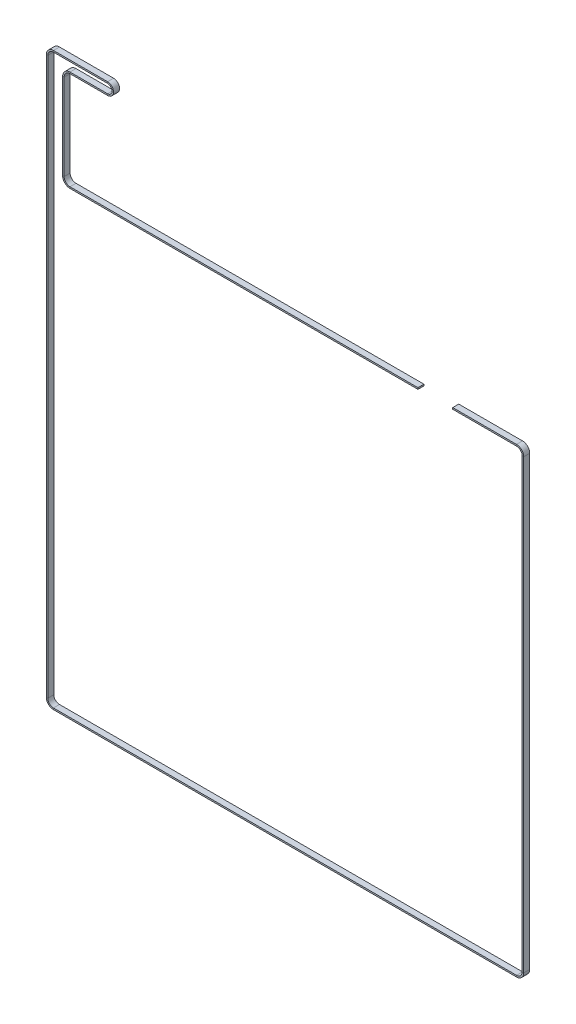
SolidWorks part; units mm, degrees
ref_plane "Front" through (0, 0, 0) normal (0, 0, 1) x (1, 0, 0)
ref_plane "Top" through (0, 0, 0) normal (0, 1, 0) x (1, 0, 0)
ref_plane "Right" through (0, 0, 0) normal (1, 0, 0) x (0, 0, -1)
sketch "Sketch1" plane through (0, -21, 4.45) normal (0, 0, 1) x (1, 0, 0)
  line L0 (10, 63.3) -> (47.5, 63.3)
  line L1 (47.5, 73.7) -> (-6.5, 73.7)
  line L2 (-12.875, 67.325) -> (-12.875, -488)
  line L3 (-6.5, -494.375) -> (455.5, -494.375)
  line L4 (461.875, -488) -> (461.875, -42.0466)
  line L5 (455.5, -35.6716) -> (391.85, -35.6716)
  line L7 (3.4, 56.7) -> (3.4, -29.2216)
  line L8 (10, -35.8216) -> (357.15, -35.8216)
  line L10 (357.15, -35.7216) -> (357.15, -39.2216) construction
  line L11 (391.85, -34.8216) -> (391.85, -28.2216) construction
  circle A0 centre (47.5, 68.5) radius 5.2 construction
  circle A1 centre (10, 56.7) radius 6.6 construction
  circle A2 centre (-6.5, 67.325) radius 6.375 construction
  circle A3 centre (10, -29.2216) radius 6.6 construction
  circle A4 centre (-6.5, -488) radius 6.375 construction
  circle A5 centre (455.5, -488) radius 6.375 construction
  circle A6 centre (455.5, -42.0466) radius 6.375 construction
  arc A7 (47.5, 73.7) -> (47.5, 63.3) centre (47.5, 68.5) cw
  arc A8 (10, 63.3) -> (3.4, 56.7) centre (10, 56.7) ccw
  arc A9 (-12.875, 67.325) -> (-6.5, 73.7) centre (-6.5, 67.325) cw
  arc A10 (-6.5, -494.375) -> (-12.875, -488) centre (-6.5, -488) cw
  arc A11 (455.5, -494.375) -> (461.875, -488) centre (455.5, -488) ccw
  arc A12 (461.875, -42.0466) -> (455.5, -35.6716) centre (455.5, -42.0466) ccw
  arc A13 (3.4, -29.2216) -> (10, -35.8216) centre (10, -29.2216) ccw
  circle A14 centre (-6.5, 67.325) radius 9 construction
  circle A15 centre (455.5, -42.0466) radius 5.9875 construction
  circle A16 centre (10, -29.2216) radius 5.9875 construction
  dimension "D1" = 12.75
ref_plane "Plane1" through (391.85, -56.6716, 4.45) normal (-1, 0, 0) x (0, 0, 1)
sketch "Sketch2" plane through (391.85, -56.6716, 4.45) normal (-1, 0, 0) x (0, 0, 1)
  line L1 (-3, 0.75) -> (3, 0.75)
  line L2 (-3, 0.75) -> (-3, -0.75)
  line L3 (-3, -0.75) -> (3, -0.75)
  line L4 (3, 0.75) -> (3, -0.75)
  line L5 (-3, 0.75) -> (3, -0.75) construction
  line L6 (-3, -0.75) -> (3, 0.75) construction
  point P0 (0, 0)
  dimension "D1" = 6
  dimension "D2" = 1.5
sweep "Sweep1" add profiles "Sketch2" path "Sketch1"
